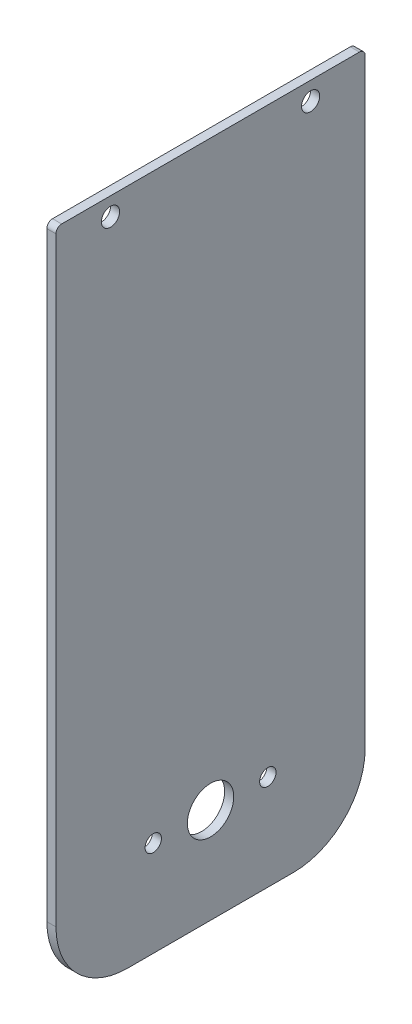
SolidWorks part; units mm, degrees
material "6061-T6 (SS)"
ref_plane "Front Plane" through (0, 0, 0) normal (0, 0, 1) x (1, 0, 0)
ref_plane "Top Plane" through (0, 0, 0) normal (0, 1, 0) x (1, 0, 0)
ref_plane "Right Plane" through (0, 0, 0) normal (1, 0, 0) x (0, 0, -1)
sketch "Sketch1" plane through (0, 0, 0) normal (1, 0, 0) x (0, 0, -1)
  line L0 (-53.975, -84.9275) -> (53.975, -84.9275) construction
  line L1 (-53.975, 118.2675) -> (53.975, 118.2675)
  line L2 (-53.975, 118.2675) -> (-53.975, -118.2675)
  line L3 (-53.975, -118.2675) -> (53.975, -118.2675)
  line L4 (53.975, 118.2675) -> (53.975, -118.2675)
  line L5 (-53.975, 118.2675) -> (53.975, -118.2675) construction
  line L6 (-53.975, -118.2675) -> (53.975, 118.2675) construction
  line L7 (-53.975, 111.9175) -> (53.975, 111.9175) construction
  line L8 (-34.925, 111.9175) -> (-34.925, 115.0925) construction
  line L9 (34.925, 111.9175) -> (34.925, 115.0925) construction
  line L10 (-53.975, 111.9175) -> (-34.925, 111.9175) construction
  line L11 (34.925, 111.9175) -> (53.975, 111.9175) construction
  circle A0 centre (0, -84.9275) radius 8.1
  circle A1 centre (20, -84.9275) radius 2.86
  circle A2 centre (-20, -84.9275) radius 2.86
  circle A3 centre (-34.925, 111.9175) radius 3.175
  circle A4 centre (34.925, 111.9175) radius 3.175
  point P0 (0, 0)
  dimension "D4" = 16.2
  dimension "D6" = 5.72
  dimension "D7" = 5.72
  dimension "D9" = 6.35
  dimension "D1" = 236.535
  dimension "D2" = 107.95
  dimension "D3" = 33.34
  dimension "D5" = 20
  dimension "D8" = 20
  dimension " 1in/2" = 6.35
  dimension "D10" = 19.05
  dimension "D11" = 19.05
extrude "Boss-Extrude1" add sketch "Sketch1" along normal blind 3.175
fillet "Fillet1" radius 25 2 edges at (1.5875, -118.2675, 53.975) (1.5875, -118.2675, -53.975)
fillet "Fillet2" radius 2 2 edges at (1.5875, 118.2675, 53.975) (1.5875, 118.2675, -53.975)
